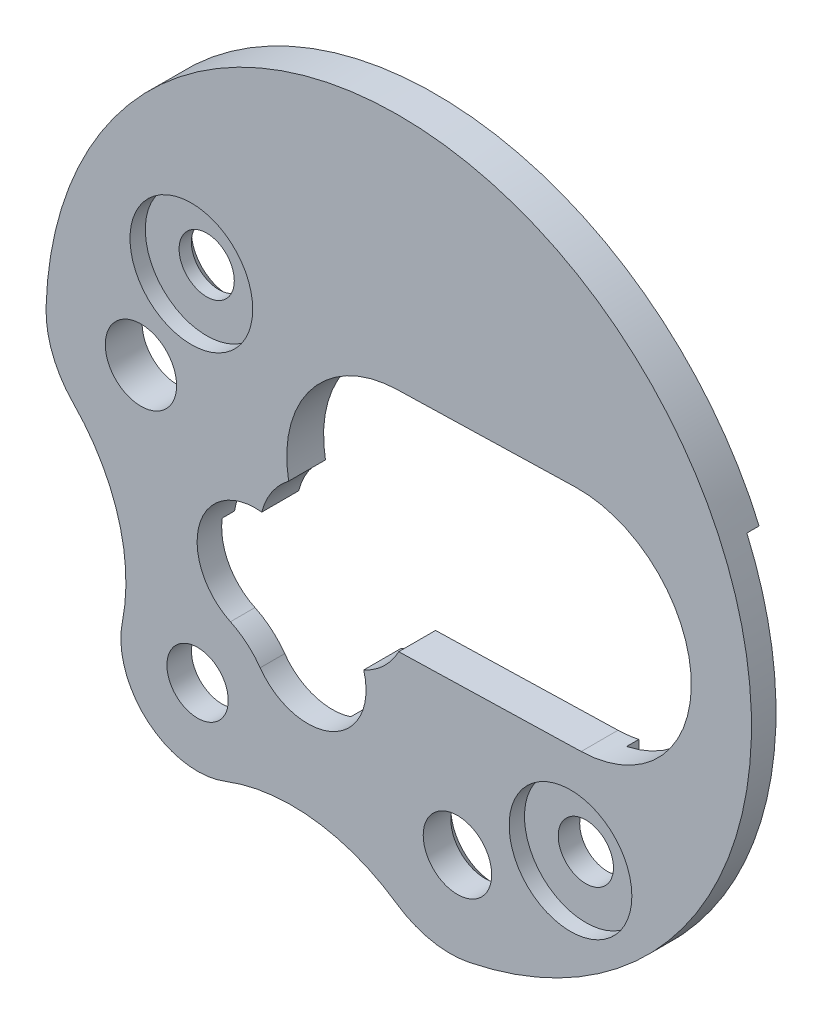
SolidWorks part; units mm, degrees
ref_plane "Alzado" through (0, 0, 0) normal (0, 0, 1) x (1, 0, 0)
ref_plane "Planta" through (0, 0, 0) normal (0, 1, 0) x (1, 0, 0)
ref_plane "Vista lateral" through (0, 0, 0) normal (1, 0, 0) x (0, 0, -1)
ref_plane "Plane1" through (0, 0, 0) normal (0, 0, -1) x (-1, 0, 0)
sketch "Sketch1" plane through (0, 0, 0) normal (0, 0, -1) x (-1, 0, 0)
  line L0 (-10.3629, -5.7271) -> (-13.3373, -5.6488)
  line L1 (-13.2403, -1.9638) -> (-10.3327, -2.0403)
  arc A0 (-10.7398, -9.6422) -> (-7.5367, -8.9707) centre (-8.6224, -11.7674) cw
  arc A1 (-7.5367, -8.9707) -> (-5.8587, -7.5604) centre (-7.0844, -7.8054) ccw
  arc A2 (-5.8587, -7.5604) -> (-4.6459, -4.5206) centre (-2.9169, -6.9722) cw
  arc A3 (-4.6459, -4.5206) -> (-10.7398, -9.6422) centre (-10.3629, -3.9046) ccw
  arc A4 (-8.1309, -4.8733) -> (-7.6199, -6.676) centre (-8.027, -5.8176) cw
  arc A5 (-7.6199, -6.676) -> (-8.1048, -7.0835) centre (-7.0844, -7.8054) ccw
  arc A6 (-8.1048, -7.0835) -> (-9.7927, -6.2699) centre (-8.8804, -6.5348) cw
  arc A7 (-9.7927, -6.2699) -> (-10.3629, -5.7271) centre (-9.2945, -5.1758) cw
  arc A8 (-13.3373, -5.6488) -> (-13.2403, -1.9638) centre (-13.2888, -3.8063) cw
  arc A9 (-10.3327, -2.0403) -> (-8.5686, -4.2174) centre (-10.3812, -3.8828) cw
  arc A10 (-8.5686, -4.2174) -> (-8.1309, -4.8733) centre (-9.2945, -5.1758) cw
  dimension "D1" = 3
  dimension "D2" = 1.25
  dimension "D3" = 3
  dimension "D4" = 5.75
  dimension "D5" = 0.95
  dimension "D6" = 1.25
  dimension "D7" = 0.95
  dimension "D8" = 1.2022
  dimension "D9" = 1.8431
  dimension "D10" = 1.8431
  dimension "D11" = 1.2022
  dimension "D12" = 1.7291
  dimension "D13" = 2.9418
  dimension "D14" = 4.6199
  dimension "D15" = 4.7031
  dimension "D16" = 5.188
  dimension "D17" = 5.2141
  dimension "D18" = 5.6518
  dimension "D19" = 6.3776
  dimension "D20" = 7.4158
  dimension "D21" = 7.446
  dimension "D22" = 7.4643
  dimension "D23" = 10.3235
extrude "Boss-Extrude1" add sketch "Sketch1" against normal blind 0.6
sketch "Sketch2" plane through (0, 0, 0) normal (0, 0, -1) x (-1, 0, 0)
  line L0 (-9.1822, -7.4356) -> (-9.5055, -7.7074)
  arc A0 (-5.4446, -5.3564) -> (-7.0871, -5.679) centre (-5.9298, -7.229) ccw
  arc A1 (-7.0871, -5.679) -> (-7.6199, -6.676) centre (-8.027, -5.8176) cw
  arc A2 (-7.6199, -6.676) -> (-8.1048, -7.0835) centre (-7.0844, -7.8054) ccw
  arc A3 (-8.1048, -7.0835) -> (-9.1822, -7.4356) centre (-8.8804, -6.5348) cw
  arc A4 (-9.5055, -7.7074) -> (-10.1952, -9.2127) centre (-8.261, -9.1882) ccw
  arc A5 (-10.1952, -9.2127) -> (-7.5367, -8.9707) centre (-8.6224, -11.7674) cw
  arc A6 (-7.5367, -8.9707) -> (-5.8587, -7.5604) centre (-7.0844, -7.8054) ccw
  arc A7 (-5.8587, -7.5604) -> (-5.4446, -5.3564) centre (-2.9169, -6.9722) cw
  dimension "D1" = 1.9344
  dimension "D2" = 0.95
  dimension "D3" = 1.25
  dimension "D4" = 0.95
  dimension "D5" = 1.9344
  dimension "D6" = 3
  dimension "D7" = 1.25
  dimension "D8" = 3
  dimension "D9" = 0.0832
  dimension "D10" = 0.5328
  dimension "D11" = 0.5355
  dimension "D12" = 1.6902
  dimension "D13" = 1.7613
  dimension "D14" = 0.4849
  dimension "D15" = 0.641
  dimension "D16" = 1.5623
  dimension "D17" = 1.8856
extrude "Cut-Extrude1" cut sketch "Sketch2" against normal blind 0.2
sketch "Sketch3" plane through (0, 0, 0) normal (0, 0, -1) x (-1, 0, 0)
  arc A0 (-13.2403, -1.9638) -> (-13.3373, -5.6488) centre (-13.2888, -3.8063) ccw construction
  arc A1 (-13.2403, -1.9638) -> (-13.3373, -5.6488) centre (-13.2888, -3.8063) ccw construction
  circle A2 centre (-18.6968, -5.5953) radius 5.02
  point P6 (-18.6968, -5.5953)
  dimension "D1" = 1.789
  dimension "D2" = 5.408
  dimension "D3" = 10.04
extrude "Cut-Extrude2" cut sketch "Sketch3" against normal blind 0.2
ref_plane "Plane2" through (0, -2.0833, 0) normal (0, 1, 0) x (1, 0, 0)
sketch "Sketch4" plane through (0, -2.0833, 0) normal (0, 1, 0) x (1, 0, 0)
  line L0 (7.583, 0) -> (6.983, 0)
  line L1 (6.983, 0) -> (6.983, -0.6)
  line L2 (6.983, -0.6) -> (7.983, -0.6)
  line L3 (7.983, -0.6) -> (7.983, -0.35)
  line L4 (7.983, -0.35) -> (7.433, -0.35)
  line L5 (7.433, -0.35) -> (7.433, -0.15)
  line L6 (7.433, -0.15) -> (7.583, 0)
  line L7 (6.983, 0) -> (6.983, -0.6) construction
  dimension "D1" = 0.45
  dimension "D2" = 0.6
  dimension "D3" = 1
  dimension "D4" = 0.25
  dimension "D5" = 0.45
  dimension "D6" = 0.6
revolve "Cut-Revolve1" cut sketch "Sketch4" angle 360 about L7 reverse direction yes
hole_wizard "Hole1" positions "Sketch6" profile "Sketch5" legacy
sketch "Sketch6" plane through (0, 0, 0.6) normal (0, 0, 1) x (1, 0, 0)
  point P0 (6.1614, -3.7822)
sketch "Sketch5" plane through (6.1614, -3.7822, 0.6) normal (1, 0, 0) x (0, -1, 0)
  line L0 (0, 0) -> (0, 0.6001)
  line L1 (0, 0.6001) -> (0.5813, 0.6001)
  line L2 (0.5813, 0.6001) -> (0.5813, 0)
  line L3 (0.5813, 0) -> (0, 0)
  line L4 (0, 110) -> (0, -10) construction
  dimension "Diameter" = 1.1626
  dimension "Depth" = 0.6001
hole_wizard "Hole2" positions "Sketch8" profile "Sketch7" legacy
sketch "Sketch8" plane through (0, 0, 0) normal (0, 0, -1) x (-1, 0, 0)
  point P0 (-11.3201, -8.1179)
sketch "Sketch7" plane through (11.3201, -8.1179, 0) normal (1, 0, 0) x (0, 1, 0)
  line L0 (0, 0) -> (0, 0.6)
  line L1 (0, 0.6) -> (0.558, 0.6)
  line L2 (0.558, 0.6) -> (0.558, 0)
  line L3 (0.558, 0) -> (0, 0)
  line L4 (0, 110) -> (0, -10) construction
  dimension "Diameter" = 1.1159
  dimension "Depth" = 0.6
hole_wizard "Hole3" positions "Sketch10" profile "Sketch9" legacy
sketch "Sketch10" plane through (0, 0, 0.6) normal (0, 0, 1) x (1, 0, 0)
  point P0 (7.0844, -7.8054)
sketch "Sketch9" plane through (7.0844, -7.8054, 0.6) normal (1, 0, 0) x (0, -1, 0)
  line L0 (0, 0) -> (0, 0.6001)
  line L1 (0, 0.6001) -> (0.5, 0.6001)
  line L2 (0.5, 0.6001) -> (0.5, 0)
  line L3 (0.5, 0) -> (0, 0)
  line L4 (0, 110) -> (0, -10) construction
  dimension "Diameter" = 1
  dimension "Depth" = 0.6001
hole_wizard "Hole4" positions "Sketch12" profile "Sketch11" legacy
sketch "Sketch12" plane through (0, 0, 0.6) normal (0, 0, 1) x (1, 0, 0)
  point P0 (13.1628, -7.2771)
sketch "Sketch11" plane through (13.1628, -7.2771, 0.6) normal (1, 0, 0) x (0, -1, 0)
  line L0 (0, 0) -> (0, 0.6001)
  line L1 (0, 0.6001) -> (0.45, 0.6001)
  line L2 (0.45, 0.6001) -> (0.45, 0.25)
  line L3 (0.45, 0.25) -> (1, 0.25)
  line L4 (1, 0.25) -> (1, 0)
  line L5 (1, 0) -> (0, 0)
  line L6 (0, 110) -> (0, -10) construction
  dimension "Diameter" = 0.9
  dimension "Depth" = 0.6001
  dimension "C-Bore Diameter" = 2
  dimension "C-Bore Depth" = 0.25
chamfer "Chamfer1" distance 0.15 angle 45 1 edges at (10.7621, -8.1179, 0)
fillet "Fillet1" radius 1.55 2 edges at (4.6459, -4.5206, 0.3) (10.7398, -9.6422, 0.3) tangent propagation no
